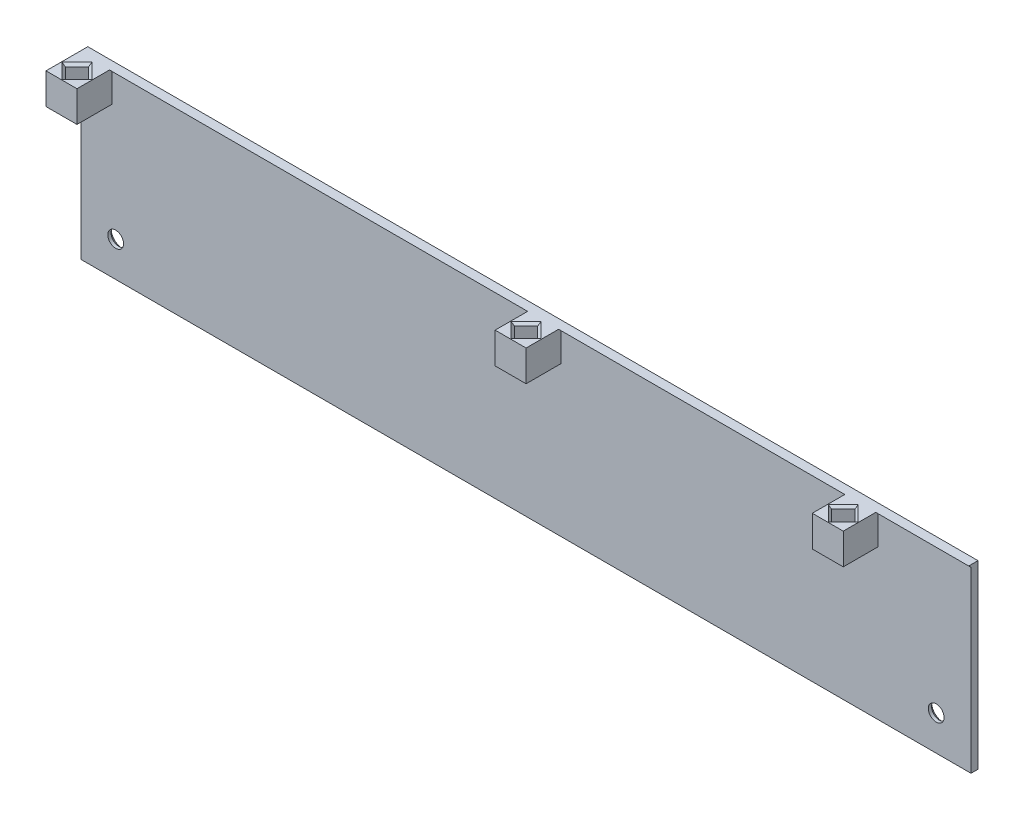
SolidWorks part; units mm, degrees
ref_plane "Front Plane" through (0, 0, 0) normal (0, 0, 1) x (1, 0, 0)
ref_plane "Top Plane" through (0, 0, 0) normal (0, 1, 0) x (1, 0, 0)
ref_plane "Right Plane" through (0, 0, 0) normal (1, 0, 0) x (0, 0, -1)
sketch "Sketch1" plane through (0, 0, 0) normal (0, 0, 1) x (1, 0, 0)
  line L1 (0, 0) -> (243.332, 0)
  line L2 (0, 0) -> (0, 49.395)
  line L3 (0, 49.395) -> (243.332, 49.395)
  line L4 (243.332, 0) -> (243.332, 49.395)
  dimension "D1" = 49.395
  dimension "D2" = 243.332
extrude "Boss-Extrude1" add sketch "Sketch1" along normal blind 1.905
sketch "Sketch2" plane through (0, 0, 1.905) normal (0, 0, 1) x (1, 0, 0)
  line L0 (243.332, 49.395) -> (0, 49.395) construction
  line L1 (0, 49.395) -> (8.4667, 49.395)
  line L2 (0, 49.395) -> (0, 40.9283)
  line L3 (0, 40.9283) -> (8.4667, 40.9283)
  line L4 (8.4667, 49.395) -> (8.4667, 40.9283)
  line L5 (122.7667, 49.395) -> (131.2333, 49.395)
  line L6 (122.7667, 49.395) -> (122.7667, 40.9283)
  line L7 (122.7667, 40.9283) -> (131.2333, 40.9283)
  line L8 (131.2333, 49.395) -> (131.2333, 40.9283)
  line L9 (243.332, 0) -> (243.332, 49.395) construction
  line L10 (209.4653, 49.395) -> (217.932, 49.395)
  line L11 (209.4653, 49.395) -> (209.4653, 40.9283)
  line L12 (209.4653, 40.9283) -> (217.932, 40.9283)
  line L13 (217.932, 49.395) -> (217.932, 40.9283)
  dimension "D1" = 114.3
  dimension "D2" = 25.4
  dimension "D4" = 8.4667
extrude "Boss-Extrude2" add sketch "Sketch2" along normal blind 9.525
sketch "Sketch3" plane through (0, 49.395, 0) normal (0, 1, 0) x (1, 0, 0)
  line L0 (1.0583, -7.1967) -> (4.2333, -4.0217)
  line L1 (1.0583, -7.1967) -> (4.2333, -10.3717)
  line L2 (4.2333, -4.0217) -> (7.4083, -7.1967)
  line L3 (4.2333, -10.3717) -> (7.4083, -7.1967)
  line L4 (1.0583, -7.1967) -> (7.4083, -7.1967) construction
  line L5 (4.2333, -4.0217) -> (4.2333, -10.3717) construction
  line L6 (123.825, -7.1967) -> (127, -4.0217)
  line L7 (123.825, -7.1967) -> (127, -10.3717)
  line L8 (127, -4.0217) -> (130.175, -7.1967)
  line L9 (127, -10.3717) -> (130.175, -7.1967)
  line L10 (123.825, -7.1967) -> (130.175, -7.1967) construction
  line L11 (127, -4.0217) -> (127, -10.3717) construction
  line L12 (210.5237, -7.1967) -> (213.6987, -4.0217)
  line L13 (210.5237, -7.1967) -> (213.6987, -10.3717)
  line L14 (213.6987, -4.0217) -> (216.8737, -7.1967)
  line L15 (213.6987, -10.3717) -> (216.8737, -7.1967)
  line L16 (210.5237, -7.1967) -> (216.8737, -7.1967) construction
  line L17 (213.6987, -4.0217) -> (213.6987, -10.3717) construction
  line L18 (8.4667, -11.43) -> (0, -11.43) construction
  line L19 (131.2333, -11.43) -> (122.7667, -11.43) construction
  line L20 (217.932, -11.43) -> (209.4653, -11.43) construction
  point P1 (4.2333, -7.1967)
  point P2 (127, -7.1967)
  point P3 (213.6987, -7.1967)
  point P13 (4.2333, -11.43)
  point P20 (127, -11.43)
  point P23 (213.6987, -11.43)
  dimension "D1" = 6.35
  dimension "D2" = 4.2333
extrude "Cut-Extrude1" cut sketch "Sketch3" against normal blind 6.35
chamfer "Chamfer1" distance 0.635 angle 45 24 edges at (212.1112, 43.045, 5.6092) (215.2862, 43.045, 5.6092) (215.2862, 43.045, 8.7842) (212.1112, 43.045, 8.7842) (2.6458, 43.045, 5.6092) (5.8208, 43.045, 5.6092) (5.8208, 43.045, 8.7842) (2.6458, 43.045, 8.7842) (125.4125, 43.045, 5.6092) (128.5875, 43.045, 5.6092) (128.5875, 43.045, 8.7842) (125.4125, 43.045, 8.7842) (212.1112, 49.395, 5.6092) (212.1112, 49.395, 8.7842) (215.2862, 49.395, 5.6092) (215.2862, 49.395, 8.7842) (2.6458, 49.395, 5.6092) (2.6458, 49.395, 8.7842) (5.8208, 49.395, 5.6092) (5.8208, 49.395, 8.7842) (128.5875, 49.395, 8.7842) (128.5875, 49.395, 5.6092) (125.4125, 49.395, 5.6092) (125.4125, 49.395, 8.7842)
sketch "Sketch4" plane through (243.332, 0, 0) normal (1, 0, 0) x (0, 0, -1)
  line L0 (-2.54, 49.395) -> (-1.905, 49.395)
  line L1 (-11.43, 49.395) -> (-1.905, 49.395) construction
  line L2 (-1.905, 0) -> (-1.905, 49.395) construction
  line L3 (-1.905, 49.395) -> (-1.905, 48.76)
  line L4 (-1.905, 48.76) -> (-2.54, 49.395)
  dimension "D1" = 0.635
extrude "Boss-Extrude3" add sketch "Sketch4" against normal up to surface (243.332 mm away) up to face at (0, 30.1078, 4.445)
sketch "Sketch5" plane through (0, 0, 0) normal (0, 0, -1) x (-1, 0, 0)
  line L0 (-243.332, 9.525) -> (-233.807, 9.525) construction
  line L1 (-243.332, 0) -> (-243.332, 49.395) construction
  line L2 (-233.807, 9.525) -> (-233.807, 0) construction
  line L3 (0, 0) -> (-243.332, 0) construction
  line L4 (0, 9.525) -> (-9.525, 9.525) construction
  line L5 (0, 49.395) -> (0, 0) construction
  line L6 (-9.525, 9.525) -> (-9.525, 0) construction
  point P13 (-9.525, 9.525)
  point P14 (-233.807, 9.525)
  dimension "D1" = 9.525
hole_wizard "#6 Clearance Hole1" positions "Sketch5" profile "Sketch6" hole size "#6" standard "ANSI Inch" end condition through all
sketch "Sketch6" plane through (233.807, 9.525, 0) normal (1, 0, 0) x (0, 1, 0)
  line L0 (0, 0) -> (0, 11.43)
  line L1 (0, 11.43) -> (2.1526, 11.43)
  line L2 (2.1526, 11.43) -> (2.1526, 1.0223)
  line L3 (2.1526, 1.0223) -> (3.175, 0)
  line L5 (3.175, 0) -> (0, 0)
  line L6 (-2.1526, 1.0223) -> (-3.175, 0) construction
  line L11 (0, -6.35) -> (0, 107.95) construction
  dimension "Thru Hole Dia." = 4.3053
  dimension "Thru Hole Depth" = 11.43
  dimension "Near C'Sink Dia." = 6.35
  dimension "Near C'Sink Angle" = 90
